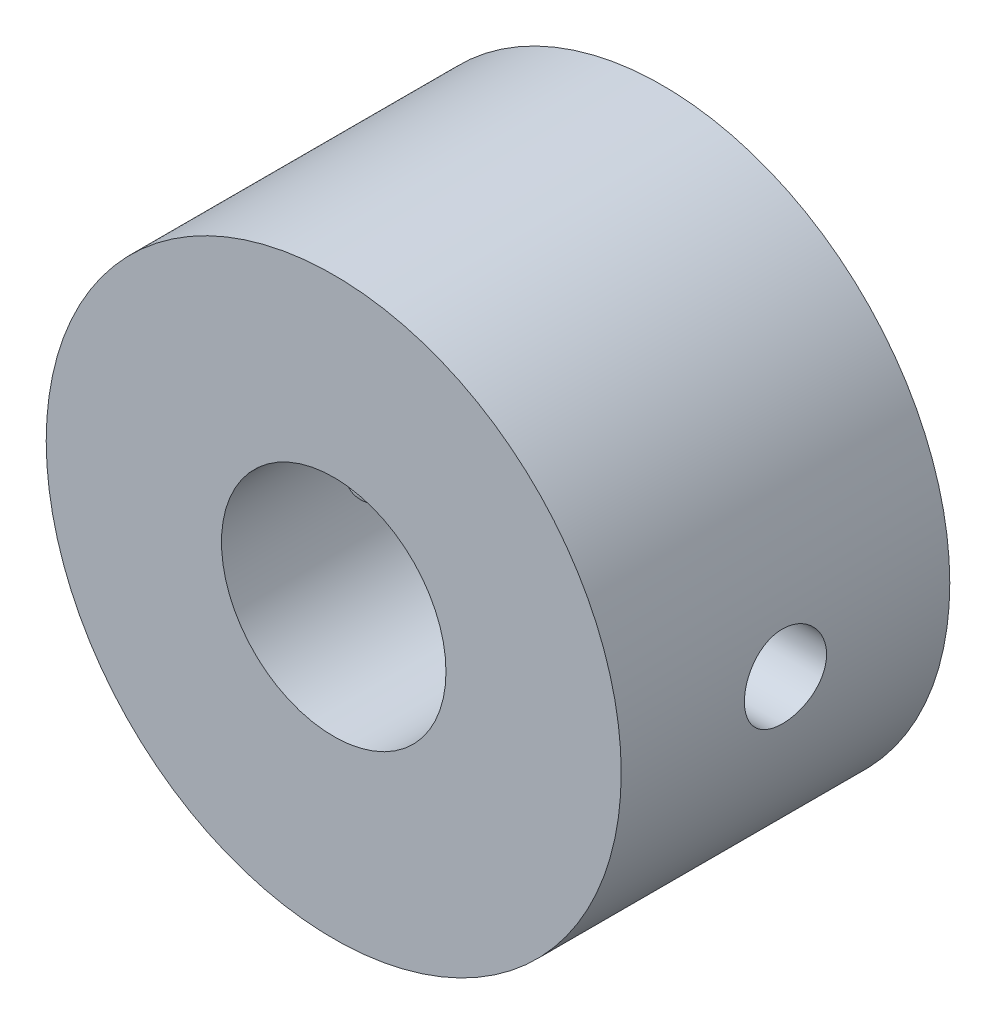
SolidWorks part; units mm, degrees
ref_plane "Front Plane" through (0, 0, 0) normal (0, 0, 1) x (1, 0, 0)
ref_plane "Top Plane" through (0, 0, 0) normal (0, 1, 0) x (1, 0, 0)
ref_plane "Right Plane" through (0, 0, 0) normal (1, 0, 0) x (0, 0, -1)
sketch "Sketch1" plane through (0, 0, 0) normal (0, 0, 1) x (1, 0, 0)
  circle A0 centre (0, 0) radius 10.5
  dimension "D1" = 21
extrude "Boss-Extrude1" add sketch "Sketch1" along normal blind 12
sketch "Sketch2" plane through (0, 0, 12) normal (0, 0, 1) x (1, 0, 0)
  circle A0 centre (0, 0) radius 4.1
  dimension "D1" = 8.2
extrude "Cut-Extrude1" cut sketch "Sketch2" against normal blind 15
sketch "Sketch3" plane through (0, 0, 0) normal (1, 0, 0) x (0, 0, -1)
  line L0 (-12, 0) -> (0, 0) construction
  line L1 (-12, 10.5) -> (-12, -10.5) construction
  line L2 (0, -10.5) -> (0, 10.5) construction
  circle A0 centre (-6, 0) radius 1.5
  dimension "D1" = 3
extrude "Cut-Extrude2" cut sketch "Sketch3" against normal through all both and the other way through all
